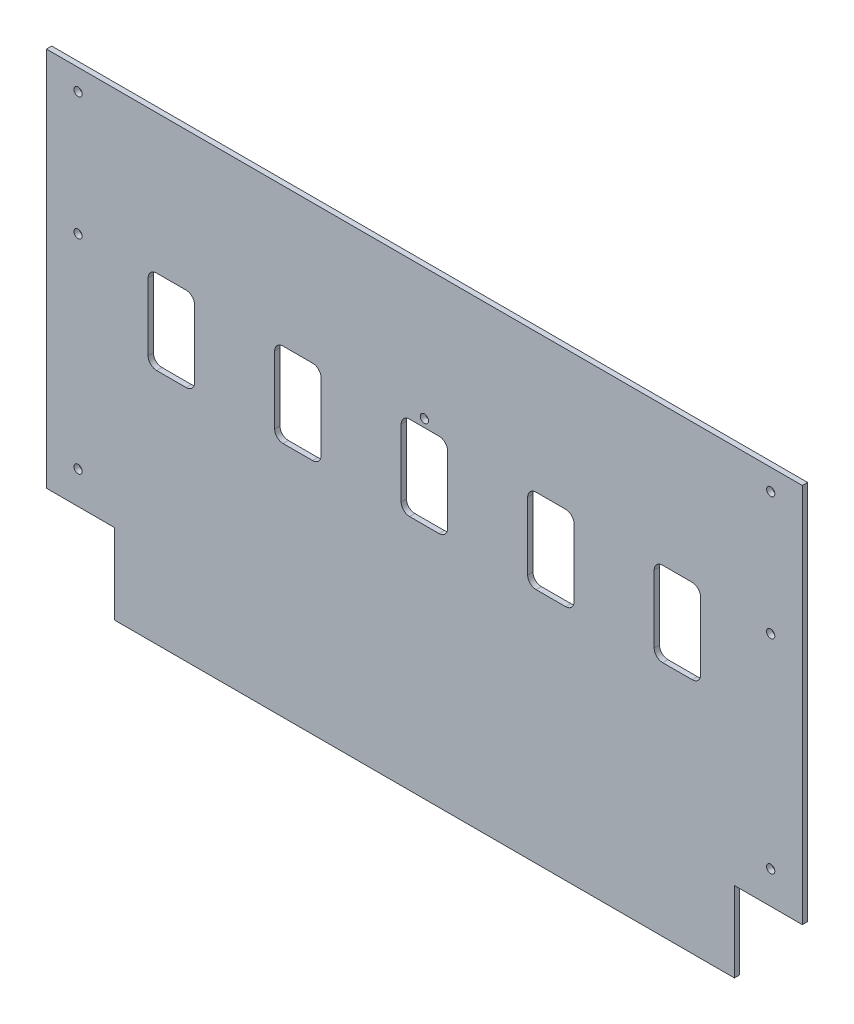
SolidWorks part; units mm, degrees
material "ABS PC"
ref_plane "Front Plane" through (0, 0, 0) normal (0, 0, 1) x (1, 0, 0)
ref_plane "Top Plane" through (0, 0, 0) normal (0, 1, 0) x (1, 0, 0)
ref_plane "Right Plane" through (0, 0, 0) normal (1, 0, 0) x (0, 0, -1)
sketch "Sketch1" plane through (0, 0, 0) normal (0, 0, 1) x (1, 0, 0)
  line L1 (-227.6475, -138.684) -> (227.6475, -138.684)
  line L2 (-227.6475, -138.684) -> (-227.6475, 138.684)
  line L3 (-227.6475, 138.684) -> (227.6475, 138.684)
  line L4 (227.6475, -138.684) -> (227.6475, 138.684)
  line L5 (0, 138.684) -> (0, -138.684) construction
  line L6 (-227.6475, 0) -> (227.6475, 0) construction
  point P0 (0, 0)
  point P4 (-159.0675, 0)
  point P5 (159.0675, 0)
  point P6 (0, 97.0788)
  point P7 (0, -97.0788)
  dimension "Width" = 277.368
  dimension "Break" = 68.58
  dimension "D2" = 68.58
  dimension "D1" = 41.6052
  dimension "D3" = 41.6052
  dimension "D4" = 455.295
sketch "Sketch2" plane through (0, 0, 0) normal (1, 0, 0) x (0, 0, -1)
  line L0 (-1.5875, -138.684) -> (1.5875, -138.684)
  dimension "Thickness" = 3.175
sketch "Sketch3" plane through (0, 0, 0) normal (0, 0, 1) x (1, 0, 0)
  line L0 (-227.6475, -138.684) -> (-227.6475, 138.684) construction
  line L1 (-227.6475, -138.684) -> (227.6475, -138.684) construction
  line L2 (227.6475, -138.684) -> (227.6475, 138.684) construction
  line L3 (-227.6475, 138.684) -> (227.6475, 138.684) construction
  line L4 (-227.6475, -138.684) -> (-227.6475, 138.684)
  line L5 (-227.6475, -138.684) -> (227.6475, -138.684)
  line L6 (227.6475, -138.684) -> (227.6475, 138.684)
  line L7 (-227.6475, 138.684) -> (227.6475, 138.684)
extrude "Boss-Extrude1" add sketch "Sketch3" along normal mid plane 3.175
sketch "Sketch4" plane through (0, 0, 1.5875) normal (0, 0, 1) x (1, 0, 0)
  line L0 (-227.6475, 29.591) -> (-158.75, 29.591) construction
  line L1 (-82.55, 29.591) -> (-82.55, 54.991) construction
  line L2 (-82.55, 54.991) -> (-90.17, 54.991) construction
  line L3 (-158.75, 29.591) -> (-158.75, 54.991) construction
  line L8 (-158.75, 29.591) -> (-82.55, 29.591) construction
  line L9 (-82.55, 29.591) -> (-6.35, 29.591) construction
  line L10 (-6.35, 29.591) -> (69.85, 29.591) construction
  line L11 (69.85, 29.591) -> (146.05, 29.591) construction
  line L12 (-82.55, 29.591) -> (-82.55, 4.191) construction
  line L13 (-82.55, 4.191) -> (-62.23, 4.191) construction
  line L16 (-158.75, 54.991) -> (-166.37, 54.991) construction
  line L17 (-158.75, 29.591) -> (-158.75, 4.191) construction
  line L18 (-158.75, 4.191) -> (-138.43, 4.191) construction
  line L19 (-6.35, 29.591) -> (-6.35, 54.991) construction
  line L20 (-161.29, 54.991) -> (-143.51, 54.991)
  line L21 (-166.37, 49.911) -> (-166.37, 9.271)
  line L22 (-161.29, 4.191) -> (-143.51, 4.191)
  line L23 (-138.43, 49.911) -> (-138.43, 9.271)
  line L24 (-6.35, 54.991) -> (-13.97, 54.991) construction
  line L25 (-6.35, 29.591) -> (-6.35, 4.191) construction
  line L26 (-6.35, 4.191) -> (13.97, 4.191) construction
  line L27 (69.85, 29.591) -> (69.85, 54.991) construction
  line L28 (-8.89, 54.991) -> (8.89, 54.991)
  line L29 (-13.97, 49.911) -> (-13.97, 9.271)
  line L30 (-8.89, 4.191) -> (8.89, 4.191)
  line L31 (13.97, 49.911) -> (13.97, 9.271)
  line L32 (69.85, 54.991) -> (62.23, 54.991) construction
  line L33 (69.85, 29.591) -> (69.85, 4.191) construction
  line L34 (69.85, 4.191) -> (90.17, 4.191) construction
  line L35 (146.05, 29.591) -> (146.05, 54.991) construction
  line L36 (67.31, 54.991) -> (85.09, 54.991)
  line L37 (62.23, 49.911) -> (62.23, 9.271)
  line L38 (67.31, 4.191) -> (85.09, 4.191)
  line L39 (90.17, 49.911) -> (90.17, 9.271)
  line L40 (146.05, 54.991) -> (138.43, 54.991) construction
  line L41 (146.05, 29.591) -> (146.05, 4.191) construction
  line L42 (146.05, 4.191) -> (166.37, 4.191) construction
  line L44 (143.51, 54.991) -> (161.29, 54.991)
  line L45 (138.43, 49.911) -> (138.43, 9.271)
  line L46 (143.51, 4.191) -> (161.29, 4.191)
  line L47 (166.37, 49.911) -> (166.37, 9.271)
  line L48 (-85.09, 54.991) -> (-67.31, 54.991)
  line L49 (-90.17, 49.911) -> (-90.17, 9.271)
  line L50 (-85.09, 4.191) -> (-67.31, 4.191)
  line L51 (-62.23, 49.911) -> (-62.23, 9.271)
  arc A0 (138.43, 9.271) -> (143.51, 4.191) centre (143.51, 9.271) ccw
  arc A1 (166.37, 9.271) -> (161.29, 4.191) centre (161.29, 9.271) cw
  arc A2 (161.29, 54.991) -> (166.37, 49.911) centre (161.29, 49.911) cw
  arc A3 (138.43, 49.911) -> (143.51, 54.991) centre (143.51, 49.911) cw
  arc A4 (62.23, 9.271) -> (67.31, 4.191) centre (67.31, 9.271) ccw
  arc A5 (90.17, 9.271) -> (85.09, 4.191) centre (85.09, 9.271) cw
  arc A6 (85.09, 54.991) -> (90.17, 49.911) centre (85.09, 49.911) cw
  arc A7 (67.31, 54.991) -> (62.23, 49.911) centre (67.31, 49.911) ccw
  arc A8 (-13.97, 9.271) -> (-8.89, 4.191) centre (-8.89, 9.271) ccw
  arc A9 (13.97, 9.271) -> (8.89, 4.191) centre (8.89, 9.271) cw
  arc A10 (8.89, 54.991) -> (13.97, 49.911) centre (8.89, 49.911) cw
  arc A11 (-8.89, 54.991) -> (-13.97, 49.911) centre (-8.89, 49.911) ccw
  arc A15 (-138.43, 9.271) -> (-143.51, 4.191) centre (-143.51, 9.271) cw
  arc A16 (-143.51, 54.991) -> (-138.43, 49.911) centre (-143.51, 49.911) cw
  arc A17 (-166.37, 49.911) -> (-161.29, 54.991) centre (-161.29, 49.911) cw
  arc A18 (-166.37, 9.271) -> (-161.29, 4.191) centre (-161.29, 9.271) ccw
  arc A19 (-90.17, 9.271) -> (-85.09, 4.191) centre (-85.09, 9.271) ccw
  arc A20 (-62.23, 9.271) -> (-67.31, 4.191) centre (-67.31, 9.271) cw
  arc A21 (-67.31, 54.991) -> (-62.23, 49.911) centre (-67.31, 49.911) cw
  arc A22 (-85.09, 54.991) -> (-90.17, 49.911) centre (-85.09, 49.911) ccw
  point P14 (-152.4, 54.991)
  point P15 (-227.6475, 29.591)
  point P16 (-76.2, 54.991)
  point P17 (-90.17, 29.591)
  point P18 (-13.97, 29.591)
  point P95 (62.23, 29.591)
  point P96 (138.43, 29.591)
  point P97 (0, 54.991)
  point P98 (76.2, 54.991)
  point P99 (152.4, 54.991)
  dimension "D1" = 5.08
  dimension "D2" = 5.08
  dimension "D8" = 27.94
  dimension "D9" = 27.94
  dimension "D10" = 27.94
  dimension "D11" = 27.94
  dimension "D12" = 27.94
  dimension "D3" = 76.2
  dimension "D4" = 76.2
  dimension "D5" = 152.4
  dimension "D6" = 152.4
  dimension "D13" = 25.4
  dimension "D14" = 25.4
extrude "Cut-Extrude1" cut sketch "Sketch4" against normal blind 25.4 contours L21 A18 L22 A15 L23 A16 L20 A17 | A22 L48 A21 L51 A20 L50 A19 L49 | L29 A8 L30 A9 L31 A10 L28 A11 | L37 A4 L38 A5 L39 A6 L36 A7 | A3 L44 A2 L47 A1 L46 A0 L45
ref_plane "Plane1" through (224.4725, -107.7083, -4.7625) normal (-1, 0, 0) x (0, 0, 1)
sketch "Sketch8" plane through (0, 0, 1.5875) normal (0, 0, 1) x (1, 0, 0)
  line L0 (0, -1.7463) -> (0, 1.7463) construction
  line L3 (-227.6475, -90.424) -> (-186.7535, -90.424)
  line L4 (-186.7535, -90.424) -> (-186.7535, -138.684)
  line L5 (-227.6475, -90.424) -> (-227.6475, -138.684)
  line L6 (227.6475, -90.424) -> (186.7535, -90.424)
  line L7 (227.6475, -138.684) -> (227.6475, 138.684) construction
  line L8 (186.7535, -90.424) -> (186.7535, -138.684)
  line L9 (-227.6475, -138.684) -> (227.6475, -138.684) construction
  line L10 (-227.6475, -138.684) -> (-186.7535, -138.684)
  line L11 (186.7535, -138.684) -> (227.6475, -138.684)
  line L12 (227.6475, -138.684) -> (227.6475, -90.424)
extrude "Cut-Extrude2" cut sketch "Sketch8" against normal blind 25.4
hole_wizard "#10 Clearance Hole1" positions "Sketch9" profile "Sketch10" hole size "#10" standard "ANSI Inch" end condition through all
sketch "Sketch9" plane through (0, 0, 1.5875) normal (0, 0, 1) x (1, 0, 0)
  point P0 (208.5975, 125.984)
  point P3 (208.5975, 51.816)
  point P6 (208.5975, -70.866)
  point P9 (-208.5975, -70.866)
  point P12 (-208.5975, 51.816)
  point P15 (-208.5975, 125.984)
sketch "Sketch10" plane through (208.5975, 125.984, 1.5875) normal (1, 0, 0) x (0, -1, 0)
  line L0 (0, 0) -> (0, 3.175)
  line L1 (0, 3.175) -> (2.4892, 3.175)
  line L2 (2.4892, 3.175) -> (2.4892, 0)
  line L5 (2.4892, 0) -> (0, 0)
  line L11 (0, -6.35) -> (0, 107.95) construction
  dimension "Thru Hole Dia." = 4.9784
  dimension "Thru Hole Depth" = 3.175
hole_wizard "#10 Clearance Hole2" positions "Sketch12" profile "Sketch13" hole size "#10" standard "ANSI Inch" end condition through all
sketch "Sketch12" plane through (0, 0, -1.5875) normal (0, 0, -1) x (-1, 0, 0)
  point P0 (0, 59.7535)
sketch "Sketch13" plane through (0, 59.7535, -1.5875) normal (1, 0, 0) x (0, 1, 0)
  line L0 (0, 0) -> (0, 3.175)
  line L1 (0, 3.175) -> (2.4892, 3.175)
  line L2 (2.4892, 3.175) -> (2.4892, 0)
  line L5 (2.4892, 0) -> (0, 0)
  line L11 (0, -6.35) -> (0, 107.95) construction
  dimension "Thru Hole Dia." = 4.9784
  dimension "Thru Hole Depth" = 3.175
equation "\"D1@Boss-Extrude1\" = \"Thickness@Sketch2\""
equation "\"D2@Sketch1\" = \"Break@Sketch1\""
equation "\"D1@Sketch1\"=\"Width@Sketch1\"*0.15"
equation "\"D3@Sketch1\"=\"D1@Sketch1\""
equation "\"SlotWidth\"= 1.1in"
equation "\"D8@Sketch4\"=\"SlotWidth\""
equation "\"D9@Sketch4\"=\"SlotWidth\""
equation "\"D10@Sketch4\"=\"SlotWidth\""
equation "\"D11@Sketch4\"=\"SlotWidth\""
equation "\"D12@Sketch4\"=\"SlotWidth\""
